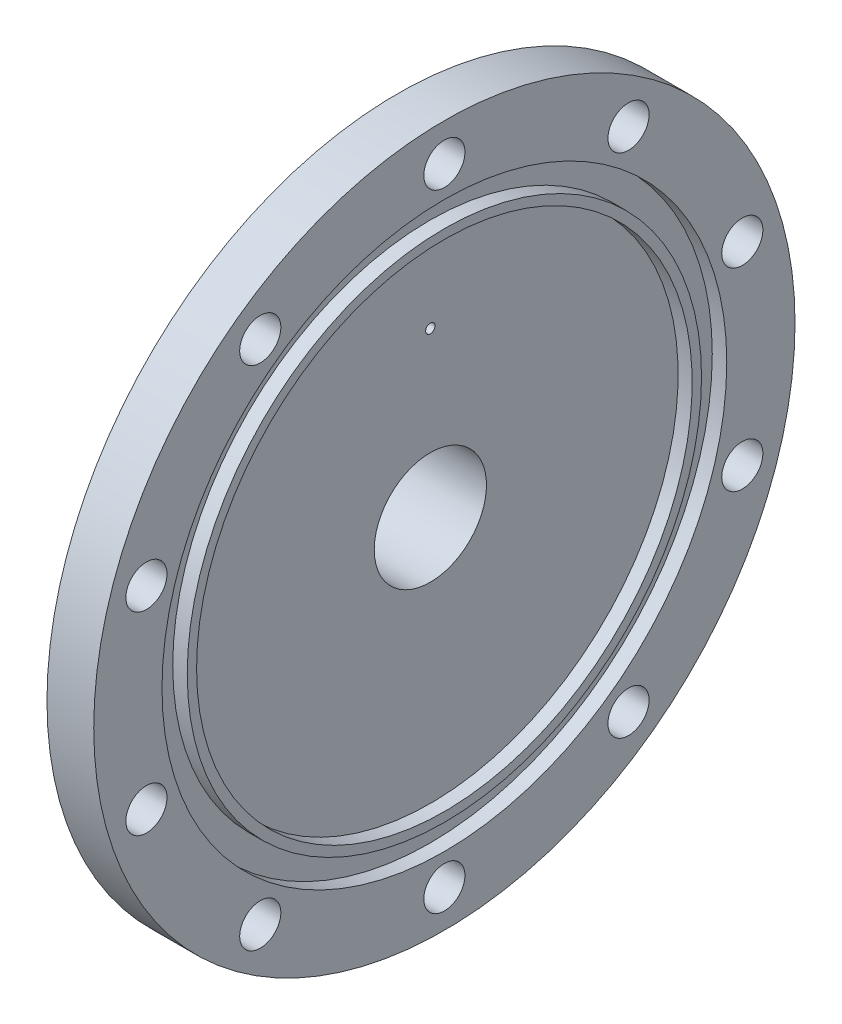
SolidWorks part; units mm, degrees
ref_plane "Front Plane" through (0, 0, 0) normal (0, 0, 1) x (1, 0, 0)
ref_plane "Top Plane" through (0, 0, 0) normal (0, 1, 0) x (1, 0, 0)
ref_plane "Right Plane" through (0, 0, 0) normal (1, 0, 0) x (0, 0, -1)
sketch "Sketch1" plane through (0, 0, 0) normal (0, 0, 1) x (1, 0, 0)
  line L0 (0, 0) -> (86.9024, 0) construction
  line L1 (0, 12) -> (17, 12)
  line L2 (0, 12) -> (0, 24)
  line L3 (0, 24) -> (10, 24)
  line L5 (10, 75) -> (20, 75)
  line L6 (10, 24) -> (10, 75)
  line L8 (20, 75) -> (20, 60.4)
  line L9 (20, 53) -> (17, 53)
  line L10 (17, 53) -> (17, 12)
  line L11 (20, 55) -> (16.9, 55)
  line L12 (16.9, 55) -> (16.9, 60.4)
  line L13 (16.9, 60.4) -> (20, 60.4)
  line L14 (20, 55) -> (20, 53)
  point P5 (20, 53.2)
  dimension "D2" = 2
  dimension "D3" = 12
  dimension "D4" = 12
  dimension "D5" = 3
  dimension "D6" = 75
  dimension "D7" = 10
  dimension "D8" = 3.1
  dimension "D9" = 5.4
  dimension "D10" = 20
  dimension "D11" = 17
  dimension "D12" = 53
  dimension "D13" = 0.2
revolve "Revolve1" add sketch "Sketch1" angle 360 about L0
sketch "Sketch2" plane through (0, 0, 0) normal (-1, 0, 0) x (0, 0, 1)
  circle A0 centre (0, 0) radius 18 construction
  circle A1 centre (0, 18) radius 2.1
extrude "Cut-Extrude1" cut sketch "Sketch2" against normal blind 6
pattern_circular "CirPattern1" count 6 over 360 about axis through (0, 0, 0) along (-1, 0, 0) of "Cut-Extrude1"
sketch "Sketch3" plane through (10, 0, 0) normal (-1, 0, 0) x (0, 0, 1)
  circle A0 centre (0, 0) radius 67 construction
  circle A1 centre (0, 67) radius 4.4
extrude "Cut-Extrude2" cut sketch "Sketch3" against normal up to next
pattern_circular "CirPattern2" count 10 over 360 about axis through (10, 0, 0) along (-1, 0, 0) of "Cut-Extrude2"
sketch "Sketch4" plane through (10, 0, 0) normal (-1, 0, 0) x (0, 0, 1)
  line L0 (-21.8435, 9.9429) -> (-8.6464, 38.9357)
  line L1 (0, 0) -> (0, 15.5415) construction
  line L2 (21.8435, 9.9429) -> (8.6464, 38.9357)
  circle A0 centre (0, 35) radius 5.5
  arc A1 (8.6464, 38.9357) -> (-8.6464, 38.9357) centre (0, 35) ccw
  arc A3 (21.8435, 9.9429) -> (-21.8435, 9.9429) centre (0, 0) ccw
  dimension "D1" = 35
extrude "Boss-Extrude1" add sketch "Sketch4" along normal blind 10
sketch "Sketch5" plane through (10, 0, 0) normal (-1, 0, 0) x (0, 0, 1)
  circle A0 centre (0, 35) radius 5.5
extrude "Cut-Extrude3" cut sketch "Sketch5" against normal blind 3
sketch "Sketch6" plane through (13, 0, 0) normal (-1, 0, 0) x (0, 0, 1)
  circle A0 centre (0, 35) radius 1
extrude "Cut-Extrude4" cut sketch "Sketch6" against normal up to next
